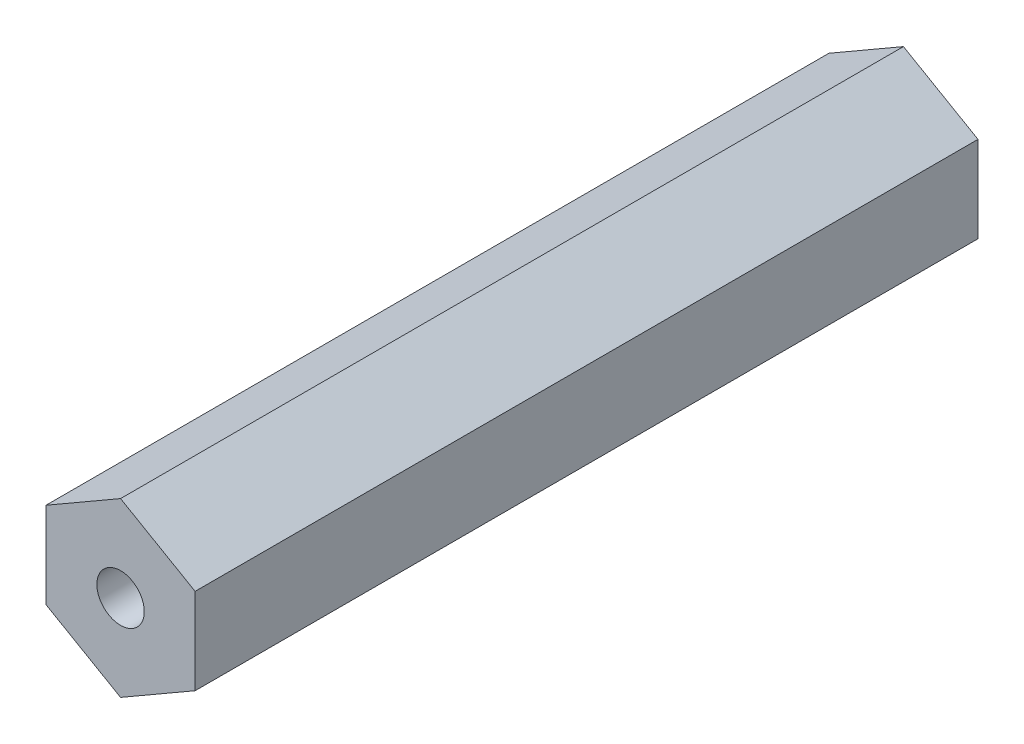
SolidWorks part; units mm, degrees
other "Markup1"
sketch "Sketch3" plane through (6.35, 7.3323, -19.05) normal (0.3384, 0.0641, -0.9388) x (-0.9259, -0.1556, -0.3443)
ref_plane "Front Plane" through (0, 0, 0) normal (0, 0, 1) x (1, 0, 0)
ref_plane "Top Plane" through (0, 0, 0) normal (0, 1, 0) x (1, 0, 0)
ref_plane "Right Plane" through (0, 0, 0) normal (1, 0, 0) x (0, 0, -1)
sketch "Sketch1" plane through (0, 0, 0) normal (0, 0, 1) x (1, 0, 0)
  line L1 (0, 7.3323) -> (-6.35, 3.6662)
  line L2 (-6.35, 3.6662) -> (-6.35, -3.6662)
  line L3 (-6.35, -3.6662) -> (0, -7.3323)
  line L4 (0, -7.3323) -> (6.35, -3.6662)
  line L5 (6.35, -3.6662) -> (6.35, 3.6662)
  line L6 (6.35, 3.6662) -> (0, 7.3323)
  circle A0 centre (0, 0) radius 6.35 construction
  dimension "D1" = 12.7
extrude "Boss-Extrude1" add sketch "Sketch1" along normal mid plane 66.675
sketch "Sketch2" plane through (0, 0, -33.3375) normal (0, 0, -1) x (-1, 0, 0)
  circle A0 centre (0, 0) radius 2.0193
  dimension "D1" = 4.0386
extrude "Cut-Extrude1" cut sketch "Sketch2" against normal through all
